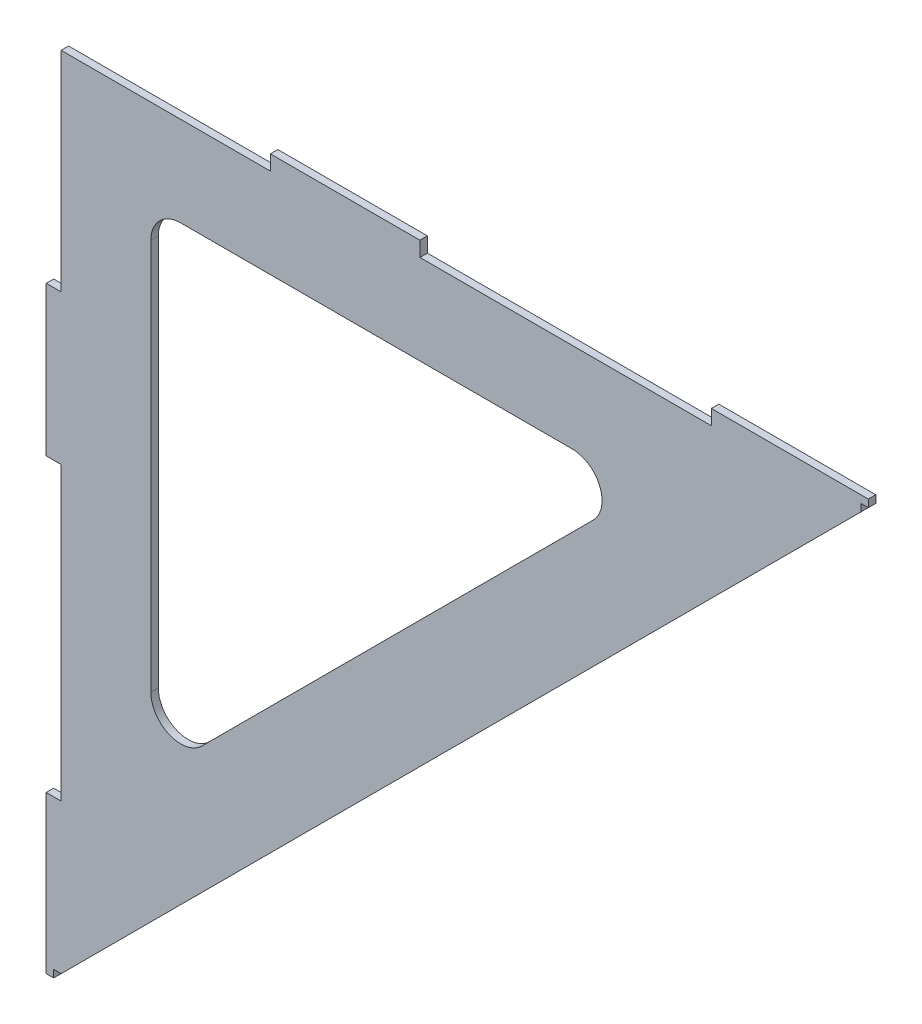
SolidWorks part; units mm, degrees
material "Mahogany"
ref_plane "Front" through (0, 0, 0) normal (0, 0, 1) x (1, 0, 0)
ref_plane "Top" through (0, 0, 0) normal (0, 1, 0) x (1, 0, 0)
ref_plane "Right" through (0, 0, 0) normal (1, 0, 0) x (0, 0, -1)
sketch "Sketch1" plane through (0, 0, 0) normal (0, 0, 1) x (1, 0, 0)
  line L0 (-135, -135) -> (-135, 135) construction
  line L1 (-137.5, -137.5) -> (137.5, -137.5) construction
  line L2 (-137.5, -137.5) -> (-137.5, 137.5) construction
  line L3 (-137.5, 137.5) -> (137.5, 137.5) construction
  line L4 (137.5, -137.5) -> (137.5, 137.5) construction
  line L5 (-137.5, -137.5) -> (137.5, 137.5) construction
  line L6 (-137.5, 137.5) -> (137.5, -137.5) construction
  line L7 (-135, 135) -> (135, 135) construction
  line L8 (135, -135) -> (135, 135) construction
  line L9 (-135, -135) -> (135, -135) construction
  line L10 (-132.5, -132.5) -> (-132.5, 132.5) construction
  line L11 (-132.5, 132.5) -> (132.5, 132.5) construction
  line L12 (132.5, -132.5) -> (132.5, 132.5) construction
  line L13 (-132.5, -132.5) -> (132.5, -132.5) construction
  line L14 (-132.5, 132.5) -> (-132.5, 62.5)
  line L15 (-132.5, 62.5) -> (-137.5, 62.5)
  line L16 (-137.5, 62.5) -> (-137.5, 12.5)
  line L17 (-137.5, 12.5) -> (-132.5, 12.5)
  line L18 (-132.5, 12.5) -> (-132.5, -85)
  line L19 (-132.5, -85) -> (-137.5, -85)
  line L20 (-137.5, -85) -> (-137.5, -137.5)
  line L21 (-137.5, -137.5) -> (-135, -137.5)
  line L22 (-135, -137.5) -> (-135, -135)
  line L23 (-135, -135) -> (-132.5, -135)
  line L24 (-132.5, -135) -> (135, 132.5)
  line L25 (135, 132.5) -> (135, 135)
  line L26 (135, 135) -> (137.5, 135)
  line L27 (137.5, 135) -> (137.5, 137.5)
  line L28 (137.5, 137.5) -> (85, 137.5)
  line L29 (85, 137.5) -> (85, 132.5)
  line L30 (85, 132.5) -> (-12.5, 132.5)
  line L31 (-12.5, 132.5) -> (-12.5, 137.5)
  line L32 (-12.5, 137.5) -> (-62.5, 137.5)
  line L33 (-62.5, 137.5) -> (-62.5, 132.5)
  line L34 (-62.5, 132.5) -> (-132.5, 132.5)
  line L35 (-102.5, 102.5) -> (62.5736, 102.5) construction
  line L36 (62.5736, 102.5) -> (-102.5, -62.5736) construction
  line L37 (-102.5, -62.5736) -> (-102.5, 102.5) construction
  line L38 (-92.5, 102.5) -> (38.4315, 102.5)
  line L39 (45.5025, 85.4289) -> (-85.4289, -45.5025)
  line L40 (-102.5, -38.4315) -> (-102.5, 92.5)
  arc A0 (-102.5, 92.5) -> (-92.5, 102.5) centre (-92.5, 92.5) cw
  arc A1 (38.4315, 102.5) -> (45.5025, 85.4289) centre (38.4315, 92.5) cw
  arc A2 (-85.4289, -45.5025) -> (-102.5, -38.4315) centre (-92.5, -38.4315) cw
  point P0 (0, 0)
  dimension "D10" = 10
  dimension "D3" = 275
  dimension "D4" = 50
  dimension "D5" = 52.5
  dimension "D6" = 97.5
  dimension "D7" = 97.5
  dimension "D8" = 30
  dimension "D9" = 30
  dimension "D1" = 2.5
  dimension "D2" = 2.5
extrude "Boss-Extrude1" add sketch "Sketch1" along normal blind 2.5
